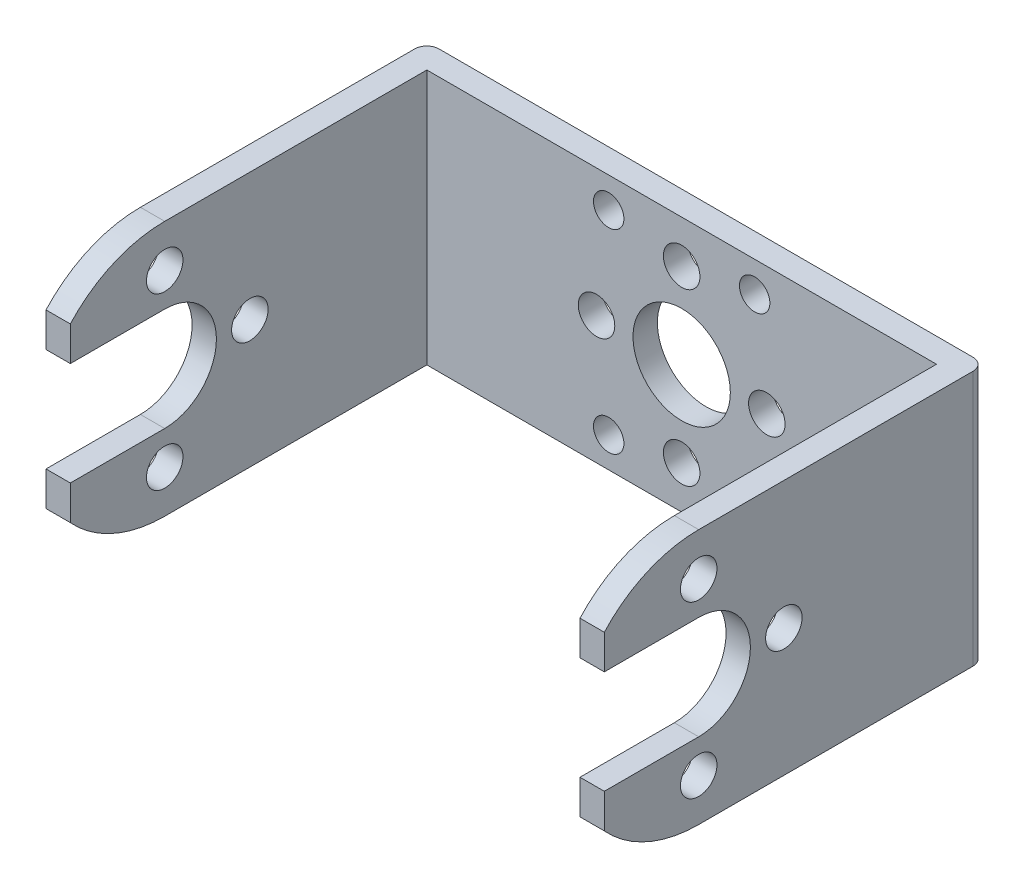
SolidWorks part; units mm, degrees
ref_plane "前视基准面" through (0, 0, 0) normal (0, 0, 1) x (1, 0, 0)
ref_plane "上视基准面" through (0, 0, 0) normal (0, 1, 0) x (1, 0, 0)
ref_plane "右视基准面" through (0, 0, 0) normal (1, 0, 0) x (0, 0, -1)
other "Configuration Table"
sketch "Sketch1" plane through (0, 0, 0) normal (0, 0, 1) x (1, 0, 0)
  line L1 (-22.95, 10.5) -> (22.95, 10.5)
  line L2 (-22.95, 10.5) -> (-22.95, -10.5)
  line L3 (-22.95, -10.5) -> (22.95, -10.5)
  line L4 (22.95, 10.5) -> (22.95, -10.5)
  line L5 (0, -10.5) -> (0, 10.5) construction
  line L6 (-22.95, 0) -> (22.95, 0) construction
  line L7 (-22.95, 10.5) -> (-20.95, 10.5)
  line L8 (-22.95, 10.5) -> (-22.95, -10.5)
  line L9 (-22.95, -10.5) -> (-20.95, -10.5)
  line L10 (-20.95, 10.5) -> (-20.95, -10.5)
  line L11 (22.95, 10.5) -> (20.95, 10.5)
  line L12 (22.95, 10.5) -> (22.95, -10.5)
  line L13 (22.95, -10.5) -> (20.95, -10.5)
  line L14 (20.95, 10.5) -> (20.95, -10.5)
  line L15 (-6, 8) -> (6, 8)
  line L16 (-6, 8) -> (-6, -8)
  line L17 (-6, -8) -> (6, -8)
  line L18 (6, 8) -> (6, -8)
  line L19 (0, -8) -> (0, 8) construction
  line L20 (-6, 0) -> (6, 0) construction
  circle A0 centre (0, 0) radius 4
  circle A1 centre (0, 0) radius 7
  circle A2 centre (-7, 0) radius 1.5
  circle A3 centre (0, 7) radius 1.5
  circle A4 centre (0, -7) radius 1.5
  circle A5 centre (7, 0) radius 1.5
  circle A6 centre (-6, 8) radius 1.25
  circle A7 centre (6, 8) radius 1.25
  circle A8 centre (-6, -8) radius 1.25
  circle A9 centre (6, -8) radius 1.25
  point P0 (0, 0)
  dimension "D5" = 21
  dimension "D1" = 21
  dimension "D2" = 45.9
  dimension "D3" = 21
  dimension "D4" = 2
  dimension "D6" = 2
  dimension "D7" = 16
  dimension "D8" = 12
extrude "Boss-Extrude1" add sketch "Sketch1" along normal blind 2 contours L14 L1 L10 L3 A5 A1 A4 A2 A3 | A5 A1 A3 A2 A4 A0 | A6 L16 A1 A3 L15 | A7 L15 A3 A1 L18 | A5 A1 L18 | A5 L18 A1 | A9 L18 A1 A4 L17 | A8 L17 A4 A1 L16 | A2 A1 L16 | A2 L16 A1 region at (0, 10.0313, 0) region at (-4.0493, 6.5768, 0) region at (-3.9737, 5.5403, 0) region at (-6.2964, 2.1612, 0) region at (4.0493, 6.5768, 0) region at (-6.2964, -2.1612, 0) region at (6.2964, 2.1612, 0) region at (-4.0493, -6.5768, 0) region at (6.2964, -2.1612, 0) region at (4.0493, -6.5768, 0)
extrude "Boss-Extrude2" add sketch "Sketch1<3>" along normal blind 31.31 contours L10 L1 L2 L3 | L1 L14 L3 L4 region at (-21.95, 0, 0) region at (21.95, 0, 0)
sketch "Sketch1<3>" plane through (0, 0, 0) normal (0, 0, 1) x (1, 0, 0) same geometry as "Sketch1"
sketch "Sketch2" plane through (-22.95, 0, 0) normal (-1, 0, 0) x (0, 0, 1)
  line L0 (0, 0) -> (23.55, 0)
  line L1 (31.31, 10.5) -> (31.31, -10.5) construction
  line L2 (23.55, 4.25) -> (31.31, 4.25)
  line L3 (23.55, 4.25) -> (23.55, -4.25)
  line L4 (23.55, -4.25) -> (31.31, -4.25)
  line L5 (31.31, 4.25) -> (31.31, -4.25)
  circle A0 centre (23.55, 0) radius 7
  circle A1 centre (23.55, 7) radius 1.5
  circle A2 centre (16.55, 0) radius 1.5
  circle A3 centre (23.55, -7) radius 1.5
  circle A4 centre (23.55, 0) radius 4.25
  circle A5 centre (23.55, 0) radius 10.5
  line M2 (0, -10.5) -> (31.31, -10.5)
  line M3 (31.31, -10.5) -> (31.31, 10.5)
  line M4 (31.31, 10.5) -> (0, 10.5)
  dimension "D1" = 8.5
  dimension "D2" = 7.76
extrude "Cut-Extrude1" cut sketch "Sketch2" against normal blind 50 contours A4 L4 A0 L2 | A0 L4 L2 M3 | A5 M3 M4 | A5 M2 M3 | A2 | A1 | A3 | A4 region at (-22.95, 9.5089, 29.439) region at (-22.95, -9.5089, 29.439) region at (-22.95, 0, 30.6284) region at (-22.95, 0, 28.3774)
fillet "Fillet1" radius 1 2 edges at (22.95, 0, 0) (-22.95, 0, 0)
